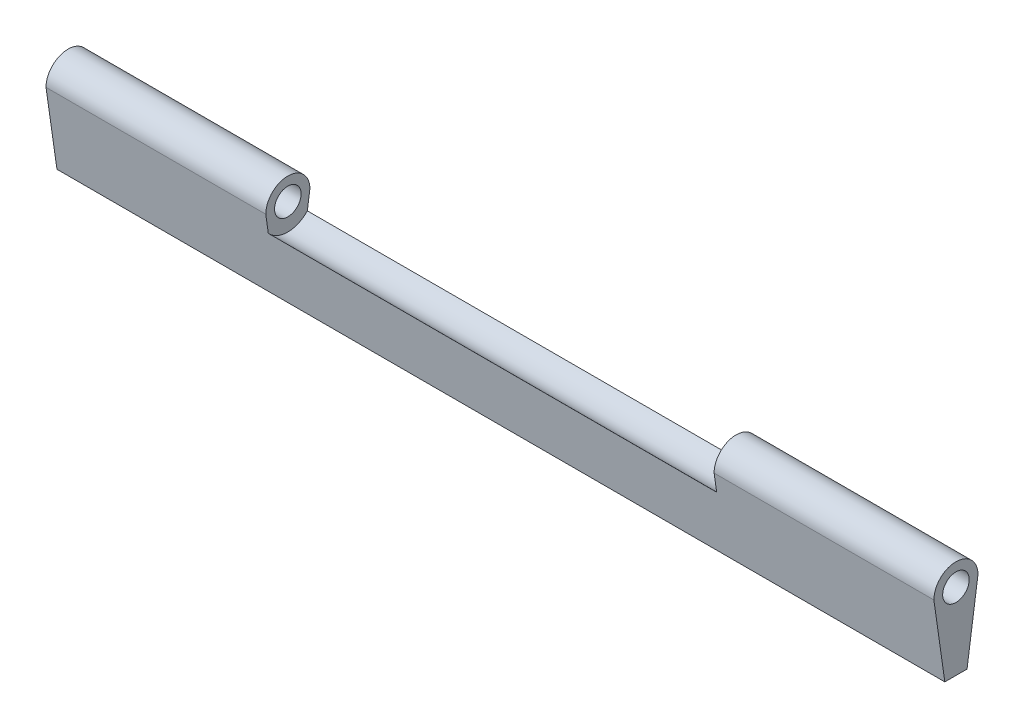
SolidWorks part; units mm, degrees
ref_plane "Front Plane" through (0, 0, 0) normal (0, 0, 1) x (1, 0, 0)
ref_plane "Top Plane" through (0, 0, 0) normal (0, 1, 0) x (1, 0, 0)
ref_plane "Right Plane" through (0, 0, 0) normal (1, 0, 0) x (0, 0, -1)
sketch "Sketch1" plane through (0, 0, 0) normal (1, 0, 0) x (0, 0, -1)
  line L0 (1.2634, -8.7) -> (2.51, 0)
  line L5 (-1.2634, -8.7) -> (1.2634, -8.7)
  line L7 (-2.51, 0) -> (-1.2634, -8.7)
  circle A0 centre (0, 0) radius 1.51
  arc A1 (2.51, 0) -> (-2.51, 0) centre (0, 0) ccw
  circle A3 centre (0, 0) radius 2.51 construction
  point P5 (0, -8.7)
  point P16 (2.51, 0)
  dimension "D1" = 3.02
  dimension "D3" = 8.7
  dimension "D4" = 2.5269
  dimension "D2" = 1
extrude "Boss-Extrude1" add sketch "Sketch1" along normal blind 25
sketch "Sketch2" plane through (25, 0, 0) normal (1, 0, 0) x (0, 0, -1)
  line L0 (-1.2634, -8.7) -> (1.2634, -8.7)
  line L1 (1.2634, -8.7) -> (2.2185, -2.0343)
  line L2 (1.2634, -8.7) -> (2.51, 0) construction
  line L3 (-2.2185, -2.0343) -> (-1.2634, -8.7)
  line L4 (-2.51, 0) -> (-1.2634, -8.7) construction
  arc A0 (-1.51, 0) -> (1.51, 0) centre (0, 0) ccw construction
  circle A1 centre (0, 0) radius 1.51 construction
  arc A2 (-2.2185, -2.0343) -> (2.2185, -2.0343) centre (0, 0) ccw
  arc A4 (-3.01, 0) -> (3.01, 0) centre (0, 0) ccw construction
  dimension "D1" = 1.5
extrude "Boss-Extrude2" add sketch "Sketch2" along normal blind 51
sketch "Sketch3" plane through (76, 0, 0) normal (1, 0, 0) x (0, 0, -1)
  line L0 (-2.51, 0) -> (-1.2634, -8.7)
  line L1 (-1.2634, -8.7) -> (1.2634, -8.7)
  line L2 (1.2634, -8.7) -> (2.51, 0)
  circle A0 centre (0, 0) radius 1.51
  arc A1 (-2.51, 0) -> (2.51, 0) centre (0, 0) cw
  arc A2 (2.51, 0) -> (-2.51, 0) centre (0, 0) ccw construction
extrude "Boss-Extrude3" add sketch "Sketch3" along normal blind 25
